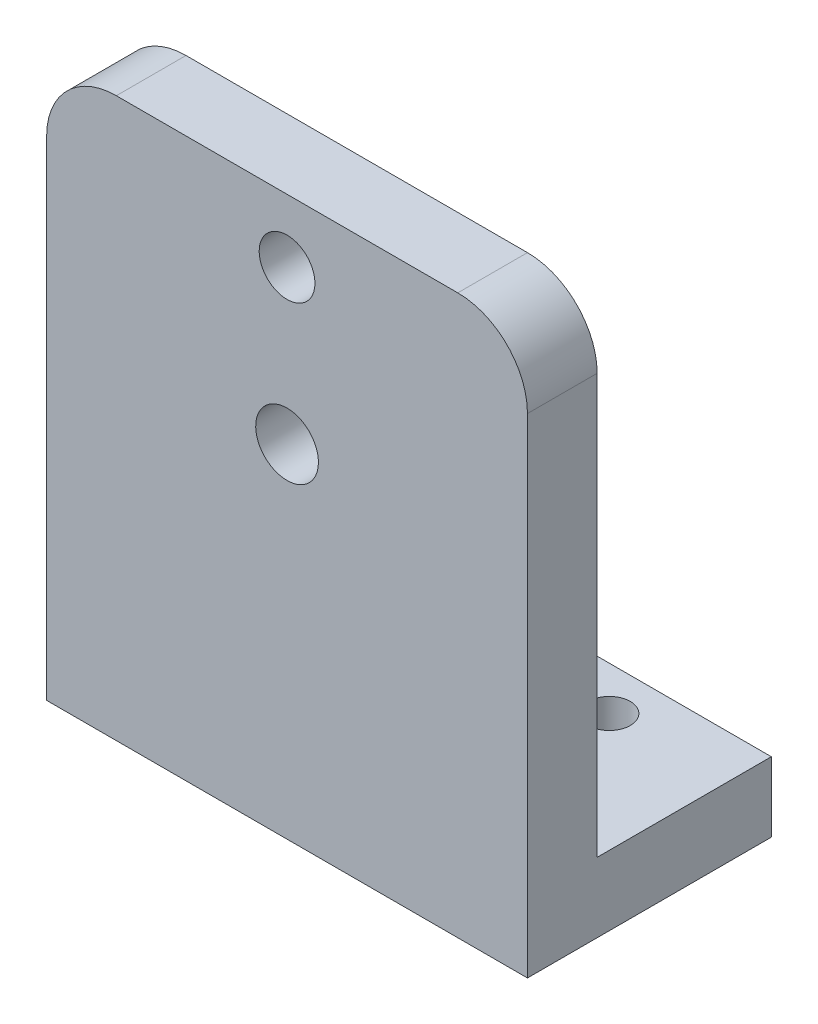
SolidWorks part; units mm, degrees
ref_plane "Front Plane" through (0, 0, 0) normal (0, 0, 1) x (1, 0, 0)
ref_plane "Top Plane" through (0, 0, 0) normal (0, 1, 0) x (1, 0, 0)
ref_plane "Right Plane" through (0, 0, 0) normal (1, 0, 0) x (0, 0, -1)
sketch "Sketch1" plane through (0, 0, 0) normal (1, 0, 0) x (0, 0, -1)
  line L0 (0, 80.15) -> (0, 0)
  line L1 (0, 0) -> (35, 0)
  line L2 (35, 0) -> (35, 10)
  line L3 (35, 10) -> (10, 10)
  line L4 (10, 10) -> (10, 80.15)
  line L5 (10, 80.15) -> (0, 80.15)
  dimension "D1" = 80.15
  dimension "D2" = 10
  dimension "D3" = 10
  dimension "D4" = 35
extrude "Boss-Extrude1" add sketch "Sketch1" along normal blind 69
sketch "Sketch2" plane through (0, 0, -10) normal (0, 0, -1) x (-1, 0, 0)
  line L0 (-34.5, 80.15) -> (-34.5, 10) construction
  line L1 (-69, 80.15) -> (0, 80.15) construction
  line L2 (-69, 10) -> (0, 10) construction
  circle A0 centre (-34.5, 71.08) radius 4
  circle A1 centre (-34.5, 49.08) radius 4.5
  dimension "D1" = 8
  dimension "D3" = 9
  dimension "D4" = 22
  dimension "D2" = 9.07
extrude "Cut-Extrude1" cut sketch "Sketch2" against normal through all
sketch "Sketch3" plane through (0, 10, 0) normal (0, 1, 0) x (1, 0, 0)
  line L3 (34.5, 35) -> (34.5, 10) construction
  line L4 (69, 35) -> (0, 35) construction
  line L5 (69, 10) -> (0, 10) construction
  line L6 (0, 22.5) -> (69, 22.5) construction
  line L7 (0, 35) -> (0, 10) construction
  line L8 (69, 35) -> (69, 10) construction
  circle A0 centre (17, 28.75) radius 3
  circle A1 centre (52, 28.75) radius 3
  circle A2 centre (52, 16.25) radius 3
  circle A3 centre (17, 16.25) radius 3
  dimension "D1" = 35
  dimension "D2" = 6
  dimension "D3" = 6.25
extrude "Cut-Extrude2" cut sketch "Sketch3" against normal blind 10
fillet "Fillet1" radius 10 2 edges at (0, 80.15, -5) (69, 80.15, -5)
